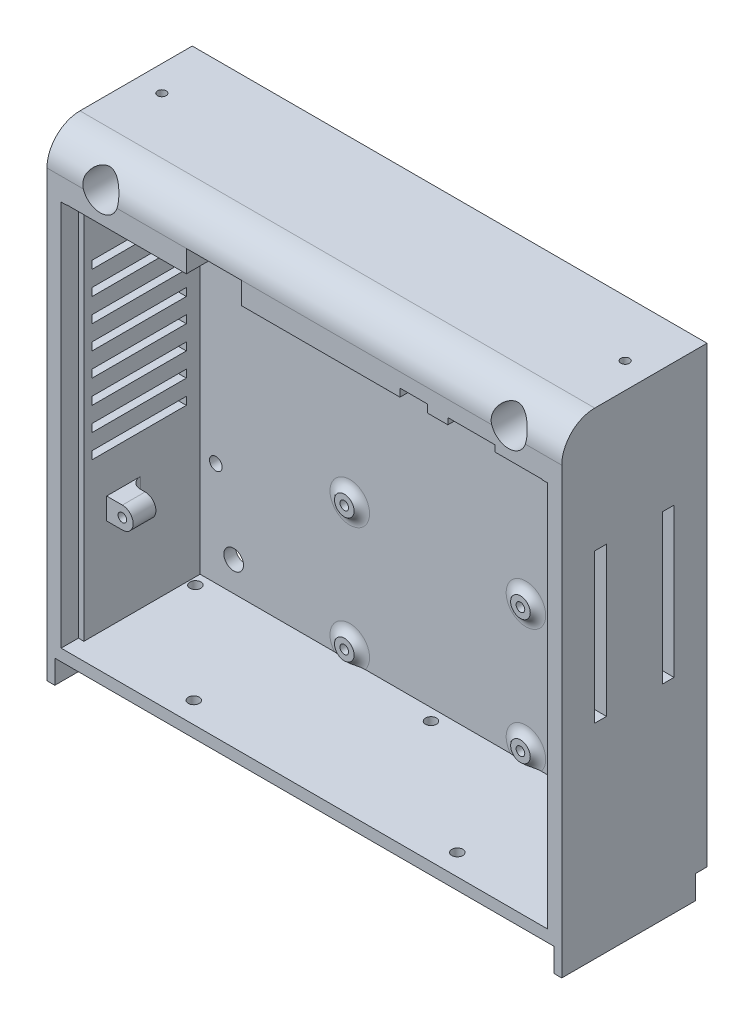
SolidWorks part; units mm, degrees
material "ABS"
ref_plane "Alzado" through (0, 0, 0) normal (0, 0, 1) x (1, 0, 0)
ref_plane "Planta" through (0, 0, 0) normal (0, 1, 0) x (1, 0, 0)
ref_plane "Vista lateral" through (0, 0, 0) normal (1, 0, 0) x (0, 0, -1)
sketch "Croquis1" plane through (0, 0, 0) normal (0, 0, 1) x (1, 0, 0)
  line L1 (0, 0) -> (131.1, 0)
  line L2 (0, 0) -> (0, 109.5)
  line L3 (0, 109.5) -> (131.1, 109.5)
  line L4 (131.1, 0) -> (131.1, 109.5)
  dimension "D1" = 131.1
  dimension "D2" = 109.5
extrude "Saliente-Extruir2" add sketch "Croquis1" along normal blind 39
sketch "Croquis2" plane through (0, 0, 39) normal (0, 0, 1) x (1, 0, 0)
  line L0 (5, 101.5) -> (35.5, 101.5)
  line L1 (126.1, 101.5) -> (126.1, 3)
  line L2 (126.1, 3) -> (5, 3)
  line L3 (5, 3) -> (5, 101.5)
  line L4 (0, 109.5) -> (0, 0) construction
  line L5 (131.1, 0) -> (131.1, 109.5) construction
  line L6 (131.1, 109.5) -> (0, 109.5) construction
  line L7 (0, 0) -> (131.1, 0) construction
  line L8 (96.9, 101.5) -> (96.9, 103.5)
  line L9 (96.9, 103.5) -> (89.9, 103.5)
  line L10 (89.9, 103.5) -> (89.9, 101.5)
  line L11 (96.9, 101.5) -> (102.1, 101.5)
  line L12 (102.1, 101.5) -> (102.1, 103.1)
  line L13 (102.1, 103.1) -> (114.1, 103.1)
  line L14 (114.1, 103.1) -> (114.1, 101.5)
  line L15 (114.1, 101.5) -> (126.1, 101.5)
  line L17 (35.5, 101.5) -> (35.5, 107.1)
  line L18 (35.5, 107.1) -> (49.5, 107.1)
  line L19 (49.5, 107.1) -> (49.5, 101.5)
  line L20 (49.5, 101.5) -> (89.9, 101.5)
  point P20 (42.5, 101.5)
  point P24 (42.5, 101.5)
  dimension "D1" = 5
  dimension "D2" = 5
  dimension "D3" = 8
  dimension "D4" = 3
  dimension "D5" = 7
  dimension "D6" = 36.2
  dimension "D7" = 2
  dimension "D8" = 24
  dimension "D9" = 12
  dimension "D10" = 1.6
  dimension "D11" = 37.5
  dimension "D12" = 7
  dimension "D13" = 5.6
extrude "Cortar-Extruir1" cut sketch "Croquis2" against normal blind 36 contours L3 L0 L17 L18 L19 L20 L10 L9 L8 L11 L12 L13 L14 L15 L1 L2
ref_plane "Plano1" through (0, 0, 21) normal (0, 0, 1) x (1, 0, 0)
sketch "Croquis3" plane through (0, 0, 3) normal (0, 0, 1) x (1, 0, 0)
  line L0 (5, 101.5) -> (126.1, 101.5) construction
  line L1 (5, 101.5) -> (5, 3) construction
  line L2 (65.55, 101.5) -> (65.55, 3) construction
  line L3 (126.1, 3) -> (5, 3) construction
  line L5 (122.1, 26.65) -> (126.1, 26.65)
  line L6 (126.1, 101.5) -> (126.1, 3) construction
  line L7 (122.1, 32.15) -> (126.1, 32.15)
  line L8 (126.1, 101.5) -> (126.1, 3) construction
  line L9 (126.1, 32.15) -> (126.1, 26.65)
  line L10 (122.1, 94.75) -> (126.1, 94.75)
  line L11 (122.1, 100.25) -> (126.1, 100.25)
  line L12 (126.1, 100.25) -> (126.1, 94.75)
  line L13 (9, 100.25) -> (5, 100.25)
  line L14 (9, 94.75) -> (5, 94.75)
  line L15 (5, 94.75) -> (5, 100.25)
  line L16 (9, 26.65) -> (5, 26.65)
  line L17 (9, 32.15) -> (5, 32.15)
  line L18 (5, 32.15) -> (5, 26.65)
  circle A0 centre (9, 97.5) radius 2.75
  circle A1 centre (9, 97.5) radius 1.1
  circle A2 centre (122.1, 97.5) radius 2.75
  circle A3 centre (122.1, 97.5) radius 1.1
  circle A4 centre (9, 29.4) radius 2.75
  circle A5 centre (9, 29.4) radius 1.1
  circle A6 centre (122.1, 29.4) radius 2.75
  circle A7 centre (122.1, 29.4) radius 1.1
  point P16 (5, 25.4)
  line M10 (126.1, 3) -> (126.1, 101.5)
  line M20 (5, 101.5) -> (5, 3)
  dimension "D1" = 4
  dimension "D2" = 5.5
  dimension "D4" = 2.2
  dimension "D3" = 4
  dimension "D5" = 76.1
  dimension "D6" = 4
extrude "Saliente-Extruir6" add sketch "Croquis3" along normal blind 5.8 from surface at 18 contours A0 A1 | A0 L13 L14 M20 | A2 A3 | L11 A2 L10 M10 | A6 A7 | A6 L5 L7 M10 | A4 A5 | A4 L17 L16 M20 starting at plane "Plano1"
fillet "Redondeo1" radius 2.8 4 edges at (126.1, 97.5, 21) (126.1, 29.4, 21) (5, 97.5, 21) (5, 29.4, 21)
sketch "Croquis4" plane through (0, 0, 39) normal (0, 0, 1) x (1, 0, 0)
  line L0 (0, 109.5) -> (131.1, 109.5)
  line L1 (131.1, 109.5) -> (131.1, 115.5)
  line L2 (131.1, 115.5) -> (0, 115.5)
  line L3 (0, 115.5) -> (0, 109.5)
  dimension "D1" = 6
extrude "Saliente-Extruir7" add sketch "Croquis4" against normal up to vertex (39 mm away) contours L3 L0 L1 L2
sketch "Croquis7" plane through (0, 0, 3) normal (0, 0, 1) x (1, 0, 0)
  circle A0 centre (122.1, 97.5) radius 1.1 construction
  circle A1 centre (122.1, 29.4) radius 1.1 construction
  circle A2 centre (9, 29.4) radius 1.1 construction
  circle A3 centre (9, 97.5) radius 1.1 construction
  circle A4 centre (122.1, 97.5) radius 1.1
  circle A5 centre (122.1, 29.4) radius 1.1
  circle A6 centre (9, 29.4) radius 1.1
  circle A7 centre (9, 97.5) radius 1.1
  circle A8 centre (9, 97.5) radius 1.6
  circle A9 centre (122.1, 97.5) radius 1.6
  circle A10 centre (122.1, 29.4) radius 1.6
  circle A11 centre (9, 29.4) radius 1.6
  dimension "D1" = 3.2
extrude "Cortar-Extruir5" cut sketch "Croquis7" against normal blind 10 contours A8 A7 | A7 | A4 | A9 A4 | A10 A5 | A5 | A6 | A11 A6
sketch "Croquis9" plane through (0, 0, 39) normal (0, 0, 1) x (1, 0, 0)
  line L4 (0, 115.5) -> (0, 0)
  line L5 (0, 0) -> (131.1, 0)
  line L6 (131.1, 0) -> (131.1, 115.5)
  line L7 (131.1, 115.5) -> (0, 115.5)
  line L8 (0, 115.5) -> (0, 0)
  line L9 (0, 0) -> (131.1, 0)
  line L10 (131.1, 0) -> (131.1, 115.5)
  line L11 (131.1, 115.5) -> (0, 115.5)
  dimension "D1" = 0
extrude "Cortar-Extruir6" cut sketch "Croquis9" against normal blind 2
sketch "Croquis10" plane through (0, 0, 37) normal (0, 0, 1) x (1, 0, 0)
  line L0 (65.55, 0) -> (65.55, 115.5) construction
  line L1 (5, 3) -> (3.6, 3)
  line L2 (5, 3) -> (5, 101.3878)
  line L3 (5, 101.3878) -> (3.6, 101.3878)
  line L4 (3.6, 3) -> (3.6, 101.3878)
  line L5 (0, 0) -> (131.1, 0) construction
  line L6 (131.1, 115.5) -> (0, 115.5) construction
  line L7 (126.1, 101.3878) -> (127.5, 101.3878)
  line L8 (127.5, 3) -> (127.5, 101.3878)
  line L9 (126.1, 3) -> (127.5, 3)
  line L10 (126.1, 3) -> (126.1, 101.3878)
  dimension "D1" = 1.4
extrude "Cortar-Extruir7" cut sketch "Croquis10" against normal blind 4.4
sketch "Croquis12" plane through (0, 0, 37) normal (0, 0, 1) x (1, 0, 0)
  line L0 (65.55, 115.5) -> (65.55, 85.6878) construction
  line L1 (131.1, 115.5) -> (0, 115.5) construction
  line L2 (25.0028, 101.5) -> (25.0028, 115.5) construction
  line L3 (35.5, 101.5) -> (5, 101.5) construction
  circle A0 centre (13.55, 108.5) radius 4.5
  circle A1 centre (117.55, 108.5) radius 4.5
  circle A2 centre (13.55, 10.5) radius 4.5
  circle A3 centre (117.55, 10.5) radius 4.5
  point P6 (25.0028, 108.5)
  dimension "D1" = 9
  dimension "D2" = 52
  dimension "D3" = 2
sketch "Croquis13" plane through (0, 0, 37) normal (0, 0, 1) x (1, 0, 0)
  circle A0 centre (13.55, 108.5) radius 2.5
  circle A1 centre (117.55, 108.5) radius 2.5
  circle A2 centre (13.55, 10.5) radius 2.5
  circle A3 centre (117.55, 10.5) radius 2.5
  dimension "D1" = 5
extrude "Cortar-Extruir9" cut sketch "Croquis13" against normal up to next
extrude "Cortar-Extruir10" cut sketch "Croquis12" against normal blind 33
fillet "Redondeo3" radius 8.4 1 edges at (65.55, 115.5, 37)
sketch "Croquis14" plane through (0, 115.5, 0) normal (0, 1, 0) x (1, 0, 0)
  line L0 (65.55, 0) -> (65.55, -28.6) construction
  line L1 (131.1, 0) -> (0, 0) construction
  line L2 (0, -28.6) -> (131.1, -28.6) construction
  circle A0 centre (6.55, -14.3) radius 2.2
  circle A1 centre (124.55, -14.3) radius 2.2
  point P9 (65.55, -14.3)
  dimension "D1" = 4.4
  dimension "D2" = 59
sketch "Croquis15" plane through (0, 115.5, 0) normal (0, 1, 0) x (1, 0, 0)
  line L0 (65.55, 0) -> (65.55, -29.7725) construction
  line L1 (131.1, 0) -> (0, 0) construction
  circle A0 centre (6.55, -14.3) radius 1.1
  circle A1 centre (124.55, -14.3) radius 1.1
  dimension "D1" = 2.2
extrude "Cortar-Extruir11" cut sketch "Croquis15" against normal up to next
sketch "Croquis16" plane through (0, 0, 3) normal (0, 0, 1) x (1, 0, 0)
  line L0 (65.55, 0) -> (65.55, 42.1815) construction
  line L1 (0, 0) -> (131.1, 0) construction
  line L2 (39.95, 3) -> (91.15, 3)
  line L3 (126.1, 3) -> (5, 3) construction
  line L4 (91.15, 3) -> (91.15, 41.1)
  line L5 (91.15, 41.1) -> (39.95, 41.1)
  line L6 (39.95, 41.1) -> (39.95, 3)
  circle A0 centre (87.98, 6.17) radius 1.1
  circle A1 centre (43.12, 6.17) radius 1.1
  circle A2 centre (87.98, 37.93) radius 1.1
  circle A3 centre (43.12, 37.93) radius 1.1
  point P9 (65.55, 3)
  point P19 (65.55, 21.0907)
  dimension "D3" = 2.2
  dimension "D6" = 3.17
  dimension "D1" = 51.2
  dimension "D2" = 38.1
  dimension "D4" = 3.17
  dimension "D5" = 3.17
  dimension "D7" = 3.17
extrude "Cortar-Extruir13" cut sketch "Croquis16" against normal up to next contours A3 | A2 | A0 | A1
sketch "Croquis17" plane through (0, 0, 3) normal (0, 0, 1) x (1, 0, 0)
  circle A0 centre (43.12, 6.17) radius 1.1 construction
  circle A1 centre (87.98, 6.17) radius 1.1 construction
  circle A2 centre (87.98, 37.93) radius 1.1 construction
  circle A3 centre (43.12, 37.93) radius 1.1 construction
  circle A4 centre (43.12, 6.17) radius 1.1
  circle A5 centre (87.98, 6.17) radius 1.1
  circle A6 centre (87.98, 37.93) radius 1.1
  circle A7 centre (43.12, 37.93) radius 1.1
  circle A8 centre (43.12, 37.93) radius 2.5
  circle A9 centre (87.98, 37.93) radius 2.5
  circle A10 centre (87.98, 6.17) radius 2.5
  circle A11 centre (43.12, 6.17) radius 2.5
  dimension "D1" = 5
extrude "Saliente-Extruir8" add sketch "Croquis17" along normal blind 1.4
fillet "Redondeo4" radius 3 4 edges at (85.48, 37.93, 3) (85.48, 6.17, 3) (40.62, 6.17, 3) (40.62, 37.93, 3)
sketch "Croquis18" plane through (0, 0, 0) normal (0, -1, 0) x (1, 0, 0)
  line L0 (0, 18.5) -> (131.1, 18.5) construction
  line L1 (0, 37) -> (0, 0) construction
  line L2 (131.1, 37) -> (131.1, 0) construction
  line L4 (63.45, 10.4) -> (67.65, 10.4)
  line L5 (63.45, 10.4) -> (63.45, 26.6)
  line L6 (63.45, 26.6) -> (67.65, 26.6)
  line L7 (67.65, 10.4) -> (67.65, 26.6)
  line L8 (63.45, 10.4) -> (67.65, 26.6) construction
  line L9 (63.45, 26.6) -> (67.65, 10.4) construction
  line L10 (46.8, 11.5) -> (51, 11.5)
  line L11 (46.8, 11.5) -> (46.8, 25.5)
  line L12 (46.8, 25.5) -> (51, 25.5)
  line L13 (51, 11.5) -> (51, 25.5)
  line L14 (46.8, 11.5) -> (51, 25.5) construction
  line L15 (46.8, 25.5) -> (51, 11.5) construction
  line L16 (99.1, 10.4) -> (103.3, 10.4)
  line L17 (99.1, 10.4) -> (99.1, 26.6)
  line L18 (99.1, 26.6) -> (103.3, 26.6)
  line L19 (103.3, 10.4) -> (103.3, 26.6)
  line L20 (99.1, 10.4) -> (103.3, 26.6) construction
  line L21 (99.1, 26.6) -> (103.3, 10.4) construction
  point P6 (65.55, 18.5)
  point P11 (57, 18.5)
  point P12 (93.1, 18.5)
  point P13 (48.9, 18.5)
  point P18 (101.2, 18.5)
  dimension "D1" = 4.2
  dimension "D2" = 16.2
  dimension "D3" = 57
  dimension "D4" = 38
  dimension "D5" = 4.2
  dimension "D6" = 14
  dimension "D7" = 6
  dimension "D8" = 4.2
  dimension "D9" = 6
extrude "Cortar-Extruir14" cut sketch "Croquis18" against normal up to next
sketch "Croquis19" plane through (0, 0, 37) normal (0, 0, 1) x (1, 0, 0)
  line L0 (0, 0) -> (57, 0)
  line L1 (0, 0) -> (131.1, 0) construction
  line L5 (0, 0) -> (0, -6)
  line L6 (0, -6) -> (2, -6)
  line L7 (2, -6) -> (2, 0)
  line L8 (131.1, 0) -> (93.1, 0)
  line L12 (131.1, 0) -> (131.1, -6)
  line L13 (131.1, -6) -> (129.1, -6)
  line L14 (129.1, -6) -> (129.1, 0)
  line L17 (59, 0) -> (91.1, 0)
  dimension "D6" = 2
extrude "Saliente-Extruir10" add sketch "Croquis19" against normal up to vertex (34 mm away)
ref_plane "Plano2" through (102.1, 101.5, 37) normal (0, -1, 0) x (-1, 0, 0)
sketch "Croquis22" plane through (0, 0, 0) normal (0, -1, 0) x (1, 0, 0)
  line L0 (0, 6) -> (131.1, 6) construction
  line L3 (0, 3) -> (0, 37) construction
  line L4 (131.1, 3) -> (131.1, 37) construction
  line L5 (0, 31.6) -> (131.1, 31.6) construction
  line L6 (2, 37) -> (129.1, 37) construction
  circle A0 centre (6.8, 6) radius 1.4
  circle A1 centre (66.8, 6) radius 1.4
  circle A3 centre (124.3, 6) radius 1.4
  circle A4 centre (32, 31.6) radius 1.4
  circle A5 centre (99.1, 31.6) radius 1.4
  point P4 (6.8, 6)
  dimension "D3" = 2.8
  dimension "D1" = 6
  dimension "D2" = 6.8
  dimension "D4" = 60
  dimension "D5" = 6.8
  dimension "D7" = 5.4
  dimension "D8" = 32
  dimension "D9" = 32
extrude "Cortar-Extruir19" cut sketch "Croquis22" against normal up to surface (3 mm away) up to face at (65.5106, 3, 18.6409)
sketch "Croquis5" plane through (0, 0, 0) normal (-1, 0, 0) x (0, 0, 1)
  line L0 (18.5, 0) -> (18.5, 106.1922) construction
  line L1 (3, 0) -> (0, 0) construction
  line L3 (6.5, 48) -> (6.5, 50)
  line L4 (6.5, 42) -> (30.5, 42)
  line L5 (6.5, 42) -> (6.5, 44)
  line L6 (6.5, 44) -> (30.5, 44)
  line L7 (30.5, 42) -> (30.5, 44)
  line L8 (6.5, 42) -> (30.5, 44) construction
  line L9 (6.5, 44) -> (30.5, 42) construction
  line L10 (6.5, 48) -> (30.5, 48)
  line L11 (30.5, 48) -> (30.5, 50)
  line L12 (6.5, 50) -> (30.5, 50)
  line L13 (6.5, 54) -> (6.5, 56)
  line L14 (6.5, 54) -> (30.5, 54)
  line L15 (30.5, 54) -> (30.5, 56)
  line L16 (6.5, 56) -> (30.5, 56)
  line L17 (6.5, 60) -> (6.5, 62)
  line L18 (6.5, 60) -> (30.5, 60)
  line L19 (30.5, 60) -> (30.5, 62)
  line L20 (6.5, 62) -> (30.5, 62)
  line L21 (6.5, 66) -> (6.5, 68)
  line L22 (6.5, 66) -> (30.5, 66)
  line L23 (30.5, 66) -> (30.5, 68)
  line L24 (6.5, 68) -> (30.5, 68)
  line L25 (6.5, 72) -> (6.5, 74)
  line L26 (6.5, 72) -> (30.5, 72)
  line L27 (30.5, 72) -> (30.5, 74)
  line L28 (6.5, 74) -> (30.5, 74)
  line L29 (6.5, 78) -> (6.5, 80)
  line L30 (6.5, 80) -> (30.5, 80)
  line L31 (30.5, 78) -> (30.5, 80)
  line L32 (6.5, 78) -> (30.5, 78)
  line L33 (6.5, 84) -> (6.5, 86)
  line L34 (6.5, 86) -> (30.5, 86)
  line L35 (30.5, 84) -> (30.5, 86)
  line L36 (6.5, 84) -> (30.5, 84)
  line L38 (0, 106.1922) -> (37, 106.1922) construction
  line L39 (0, 115.5) -> (0, 0) construction
  line L40 (37, 107.1) -> (37, -6) construction
  point P6 (18.5, 43)
  dimension "D1" = 24
  dimension "D2" = 2
  dimension "D3" = 42
  dimension "D4" = 6
  dimension "D5" = 3
extrude "Cortar-Extruir3" cut sketch "Croquis5" against normal mid plane 20
sketch "Croquis6" plane through (131.1, 0, 0) normal (1, 0, 0) x (0, 0, -1)
  line L0 (-37, 100.4035) -> (0, 100.4035) construction
  line L1 (-28.6, 46) -> (-25.6, 46)
  line L2 (-3, 0) -> (0, 0) construction
  line L3 (-28.6, 46) -> (-28.6, 84)
  line L4 (-28.6, 84) -> (-25.6, 84)
  line L5 (-25.6, 84) -> (-25.6, 46)
  line L6 (-18.5, 0) -> (-18.5, 100.4035) construction
  line L8 (-8.4, 84) -> (-11.4, 84)
  line L9 (-8.4, 46) -> (-8.4, 84)
  line L10 (-8.4, 46) -> (-11.4, 46)
  line L11 (-11.4, 84) -> (-11.4, 46)
  line L12 (-37, -6) -> (-37, 107.1) construction
  line L13 (0, 0) -> (0, 115.5) construction
  dimension "D1" = 46
  dimension "D2" = 3
  dimension "D3" = 8.4
  dimension "D4" = 38
extrude "Cortar-Extruir4" cut sketch "Croquis6" against normal blind 10
